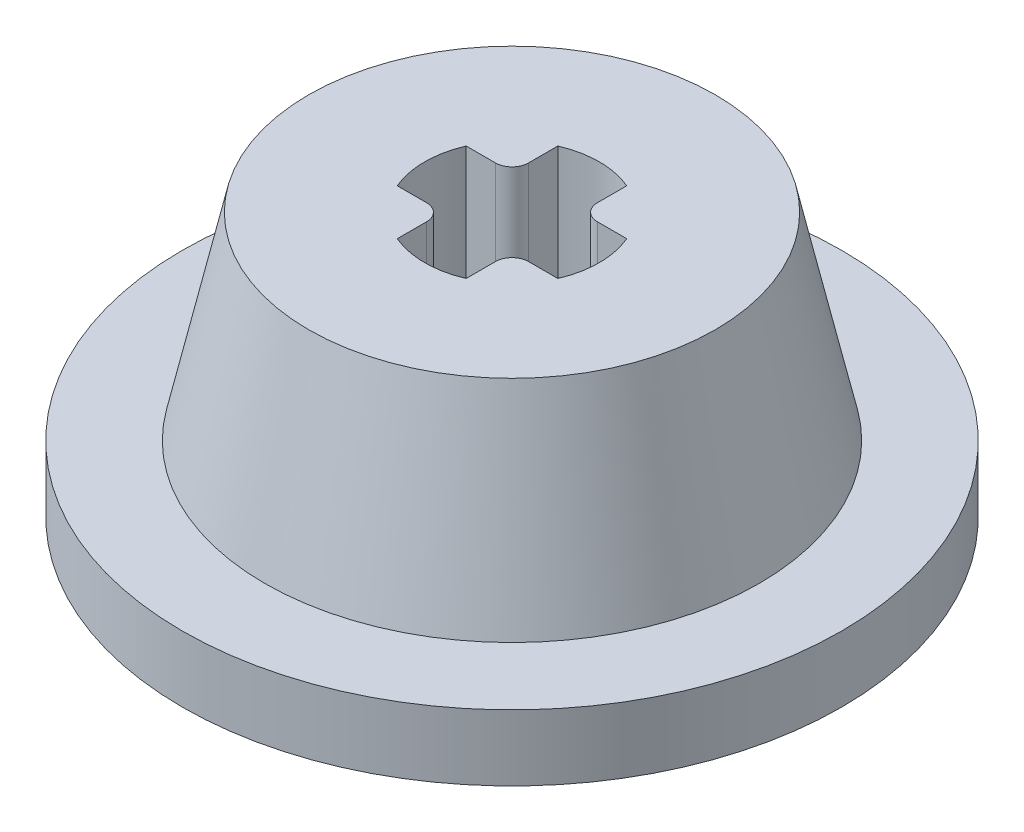
SolidWorks part; units mm, degrees
ref_plane "Front Plane" through (0, 0, 0) normal (0, 0, 1) x (1, 0, 0)
ref_plane "Top Plane" through (0, 0, 0) normal (0, 1, 0) x (1, 0, 0)
ref_plane "Right Plane" through (0, 0, 0) normal (1, 0, 0) x (0, 0, -1)
sketch "Sketch1" plane through (0, 0, 0) normal (0, 1, 0) x (1, 0, 0)
  circle A0 centre (0, 0) radius 7.5
  dimension "D1" = 15
extrude "Boss-Extrude1" add sketch "Sketch1" along normal blind 6
sketch "Sketch2" plane through (0, 0, 0) normal (1, 0, 0) x (0, 0, -1)
  line L0 (-7.5, 0) -> (-6.1698, 6)
  line L1 (7.5, 6) -> (-7.5, 6) construction
  line L2 (-6.1698, 6) -> (-7.5, 6)
  line L3 (-7.5, 6) -> (-7.5, 0)
  line L4 (0, 0) -> (0, 50000) construction
  line L5 (-7.5, 0) -> (7.5, 0) construction
  point P11 (0, 0)
  dimension "D1" = 12.5
revolve "Cut-Revolve1" cut sketch "Sketch2" angle 360 about L4
sketch "Sketch3" plane through (0, 0, 0) normal (0, -1, 0) x (-1, 0, 0)
  circle A0 centre (0, 0) radius 10
  dimension "D1" = 20
extrude "Boss-Extrude2" add sketch "Sketch3" along normal blind 2
sketch "Sketch4" plane through (0, -2, 0) normal (0, -1, 0) x (1, 0, 0)
  line L0 (1.045, -2.4353) -> (1.045, 2.4353)
  line L1 (-1.045, -2.4353) -> (-1.045, 2.4353)
  line L2 (0, 0) -> (35355.3391, 35355.3391) construction
  line L3 (0.8543, 0) -> (50000.8543, 0) construction
  line L4 (-2.4353, 1.045) -> (2.4353, 1.045)
  line L5 (-2.4353, -1.045) -> (2.4353, -1.045)
  circle A0 centre (0, 0) radius 2.65
  dimension "D1" = 5.3
  dimension "D2" = 2.09
  dimension "D3" = 45
extrude "Cut-Extrude1" cut sketch "Sketch4" against normal through all contours L1 L5 L0 L4 | L4 A0 L5 L1 | L0 A0 L1 L4 | L5 A0 L4 L0 | L1 A0 L0 L5 region at (0, -2, -1.8136) region at (0, -2, 0) region at (1.8136, -2, 0) region at (0, -2, 1.8136) region at (-1.8136, -2, 0)
fillet "Fillet1" radius 0.5 4 edges at (1.045, 2, 1.045) (1.045, 2, -1.045) (-1.045, 2, -1.045) (-1.045, 2, 1.045)
